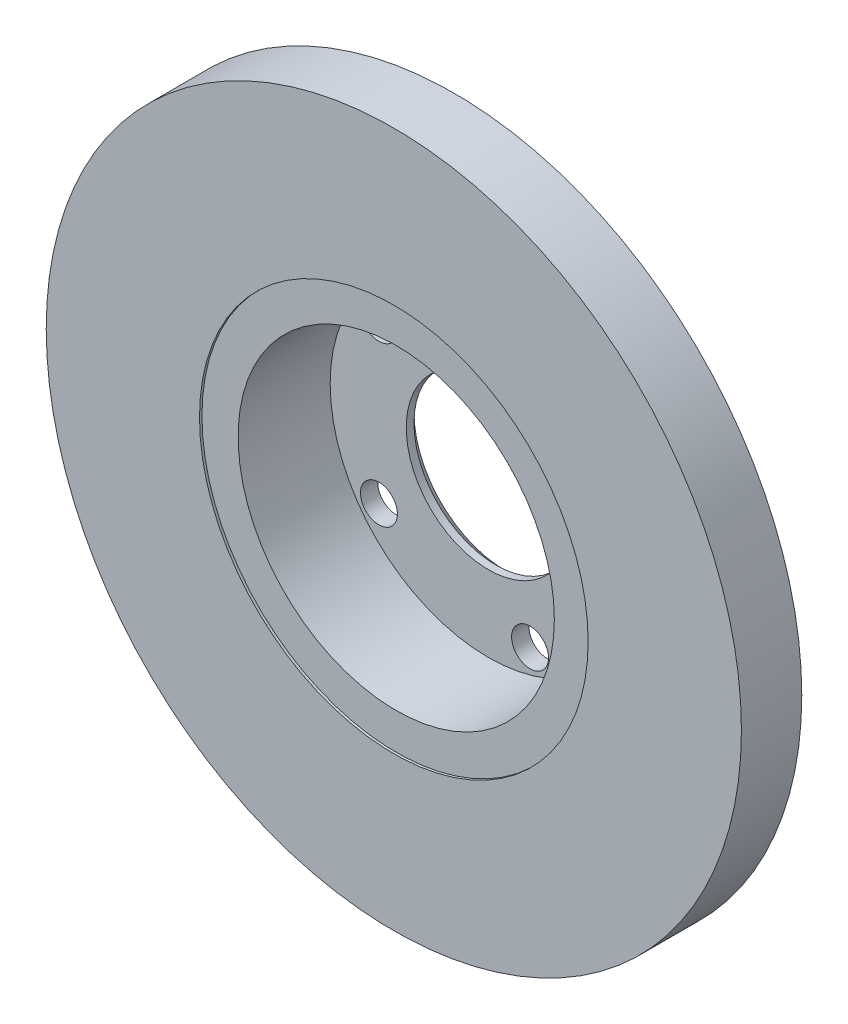
SolidWorks part; units mm, degrees
ref_plane "Front" through (0, 0, 0) normal (0, 0, 1) x (1, 0, 0)
ref_plane "Top" through (0, 0, 0) normal (0, 1, 0) x (1, 0, 0)
ref_plane "Right" through (0, 0, 0) normal (1, 0, 0) x (0, 0, -1)
ref_axis "Axis1" through (0, 0, -80.9) along (0, 0, 1)
sketch "Sketch1" plane through (0, 0, 0) normal (0, 0, 1) x (1, 0, 0)
  circle A0 centre (0, 0) radius 144
  dimension "D1" = 288
extrude "Boss-Extrude1" add sketch "Sketch1" along normal blind 10 from offset 2.5
sketch "Sketch2" plane through (0, 0, 12.5) normal (0, 0, 1) x (1, 0, 0)
  circle A0 centre (0, 0) radius 80.5
  dimension "D1" = 161
extrude "Cut-Extrude1" cut sketch "Sketch2" against normal blind 1
sketch "Sketch3" plane through (0, 0, 11.5) normal (0, 0, 1) x (1, 0, 0)
  circle A0 centre (0, 0) radius 65.5
  dimension "D1" = 131
extrude "Cut-Extrude2" cut sketch "Sketch3" against normal through all
sketch "Sketch4" plane through (0, 0, 2.5) normal (0, 0, -1) x (-1, 0, 0)
  circle A0 centre (0, 0) radius 65.5 construction
  circle A1 centre (0, 0) radius 65.5
  circle A2 centre (0, 0) radius 74.125
  dimension "D1" = 148.25
extrude "Boss-Extrude3" add sketch "Sketch4" along normal blind 36.33
sketch "Sketch5" plane through (0, 0, -33.83) normal (0, 0, -1) x (-1, 0, 0)
  circle A0 centre (0, 0) radius 74.125 construction
  circle A1 centre (0, 0) radius 74.125
extrude "Boss-Extrude4" add sketch "Sketch5" against normal blind 7.2
sketch "Sketch6" plane through (0, 0, -26.63) normal (0, 0, 1) x (1, 0, 0)
  circle A0 centre (0, 0) radius 34
  dimension "D1" = 68
extrude "Cut-Extrude3" cut sketch "Sketch6" against normal blind 17.2
sketch "Sketch7" plane through (0, 0, 2.5) normal (0, 0, -1) x (-1, 0, 0)
  circle A0 centre (0, 0) radius 144 construction
  circle A1 centre (0, 0) radius 144
  circle A2 centre (0, 0) radius 80.5
  dimension "D1" = 161
extrude "Boss-Extrude5" add sketch "Sketch7" along normal blind 15
sketch "Sketch8" plane through (0, 0, 0) normal (1, 0, 0) x (0, 0, -1)
  line L0 (0, 50) -> (0, -50) construction
  line L1 (-5, 154) -> (5, 154)
  line L2 (-5, 154) -> (-5, 132)
  line L3 (-5, 132) -> (5, 132)
  line L4 (5, 154) -> (5, 132)
  line L5 (-5, 154) -> (5, 132) construction
  line L6 (-5, 132) -> (5, 154) construction
  line L7 (12.5, -144) -> (12.5, 144) construction
  point P0 (0, 143)
  point P8 (12.5, 144)
  dimension "D1" = 22
  dimension "D2" = 10
  dimension "D3" = 12
chamfer "Chamfer2" distance 4 angle 45 1 edges at (-34, 0, -33.83)
sketch "Sketch10" plane through (0, 0, 0) normal (0, 0, 1) x (1, 0, 0)
  circle A0 centre (56, 0) radius 7.65
  circle A1 centre (0, 0) radius 65.5 construction
  dimension "D1" = 56
  dimension "D2" = 15.3
extrude "Cut-Extrude4" cut sketch "Sketch10" against normal through all
pattern_circular "CirPattern2" count 5 over 360 about axis through (0, 0, -80.9) along (0, 0, 1) of "Cut-Extrude4"
chamfer "Chamfer3" distance 2 angle 45 1 edges at (-74.125, 0, -33.83)
sketch "Sketch12" plane through (0, 0, -12.5) normal (0, 0, -1) x (-1, 0, 0)
  line L0 (0, 0) -> (-73.7773, -123.6645) construction
  line L1 (-43.0368, -72.1376) -> (-71.2156, -119.3706)
  line L2 (-43.0368, -72.1376) -> (-39.6016, -74.187)
  line L3 (-71.2156, -119.3706) -> (-67.7805, -121.42)
  line L4 (-39.6016, -74.187) -> (-67.7805, -121.42)
  line L5 (-82.6929, -15.293) -> (-137.1904, -22.7112)
  line L6 (-83.2324, -11.3296) -> (-137.7299, -18.7478)
  line L7 (-137.7299, -18.7478) -> (-137.1904, -22.7112)
  line L8 (-83.2324, -11.3296) -> (-82.6929, -15.293)
  line L9 (-63.5148, 55.1169) -> (-103.2931, 93.0996)
  line L10 (-60.7524, 58.0099) -> (-100.5308, 95.9925)
  line L11 (-100.5308, 95.9925) -> (-103.2931, 93.0996)
  line L12 (-60.7524, 58.0099) -> (-63.5148, 55.1169)
  line L13 (3.4913, 84.0227) -> (8.3859, 138.8045)
  line L14 (7.4754, 83.6667) -> (12.3701, 138.4485)
  line L15 (12.3701, 138.4485) -> (8.3859, 138.8045)
  line L16 (7.4754, 83.6667) -> (3.4913, 84.0227)
  line L17 (67.8684, 49.6577) -> (113.7502, 79.9868)
  line L18 (70.0741, 46.3208) -> (115.956, 76.6499)
  line L19 (115.956, 76.6499) -> (113.7502, 79.9868)
  line L20 (70.0741, 46.3208) -> (67.8684, 49.6577)
  line L21 (81.1392, -22.1006) -> (133.4583, -39.0626)
  line L22 (79.9056, -25.9056) -> (132.2247, -42.8676)
  line L23 (132.2247, -42.8676) -> (133.4583, -39.0626)
  line L24 (79.9056, -25.9056) -> (81.1392, -22.1006)
  line L25 (33.3105, -77.2166) -> (52.6695, -128.697)
  line L26 (29.5665, -78.6246) -> (48.9255, -130.1049)
  line L27 (48.9255, -130.1049) -> (52.6695, -128.697)
  line L28 (29.5665, -78.6246) -> (33.3105, -77.2166)
  circle A0 centre (0, 0) radius 144 construction
  point P36 (0, 0)
  dimension "D1" = 55
  dimension "D2" = 84
  dimension "D3" = 4
  dimension "D4" = 7
extrude "Cut-Extrude6" cut sketch "Sketch12" against normal blind 2
